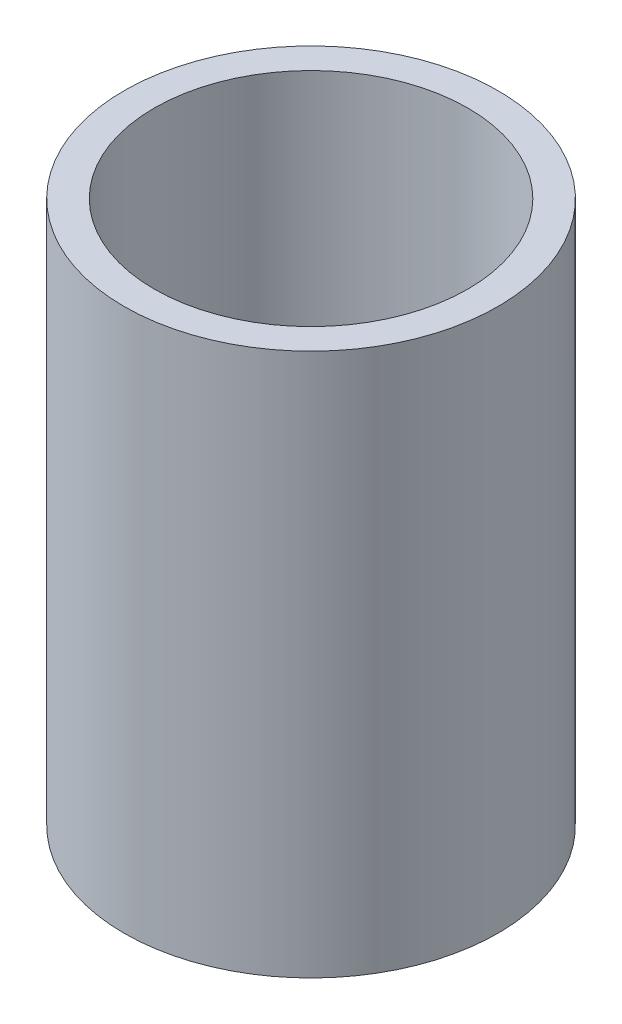
SolidWorks part; units mm, degrees
ref_plane "Front Plane" through (0, 0, 0) normal (0, 0, 1) x (1, 0, 0)
ref_plane "Top Plane" through (0, 0, 0) normal (0, 1, 0) x (1, 0, 0)
ref_plane "Right Plane" through (0, 0, 0) normal (1, 0, 0) x (0, 0, -1)
sketch "Sketch1" plane through (0, 0, 0) normal (0, 1, 0) x (1, 0, 0)
  circle A0 centre (0, 0) radius 35
  dimension "SLEEVE_OD" = 70
extrude "Boss-Extrude1" add sketch "Sketch1" along normal blind 101.6331
sketch "Sketch2" plane through (0, 0, 0) normal (0, 1, 0) x (1, 0, 0)
  circle A0 centre (0, 0) radius 29.3631
  dimension "BORE_D" = 58.7261
extrude "Cut-Extrude1" cut sketch "Sketch2" along normal through all
chamfer "Chamfer1" distance 3.9643 angle 45 rebuild error yes
